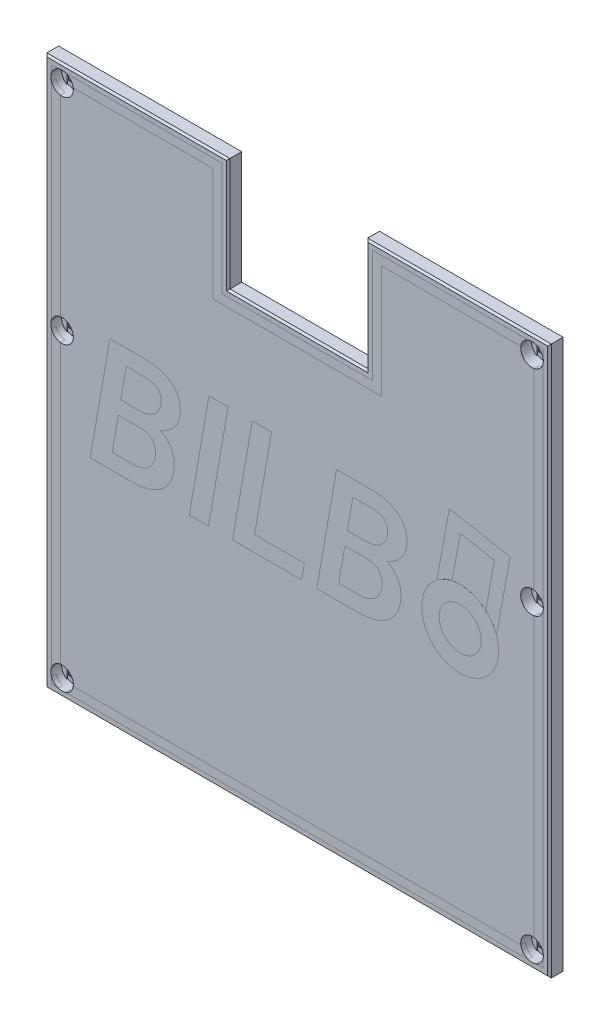
SolidWorks part; units mm, degrees
ref_plane "Front Plane" through (0, 0, 0) normal (0, 0, 1) x (1, 0, 0)
ref_plane "Top Plane" through (0, 0, 0) normal (0, 1, 0) x (1, 0, 0)
ref_plane "Right Plane" through (0, 0, 0) normal (1, 0, 0) x (0, 0, -1)
sketch "Sketch1" plane through (0, 0, 0) normal (0, 0, 1) x (1, 0, 0)
  line L0 (48, -68) -> (-48, -68) construction
  line L1 (56, -32.5) -> (56, -60) construction
  line L2 (56, 46) -> (56, -24.5) construction
  line L3 (-56, -24.5) -> (-56, 46) construction
  line L5 (-15, 54.4) -> (-15, 29) construction
  line L6 (-15, 29) -> (15, 29) construction
  line L8 (48, 54) -> (15, 54) construction
  line L9 (48, -68) -> (-48, -68) construction
  line L10 (56, -32.5) -> (56, -60) construction
  line L11 (56, 46) -> (56, -24.5) construction
  line L12 (-56, -24.5) -> (-56, 46) construction
  line L14 (-15, 54.4) -> (-15, 29) construction
  line L15 (-15, 29) -> (15, 29) construction
  line L16 (15, 29) -> (15, 54) construction
  line L17 (48, 54) -> (15, 54) construction
  line L18 (-15.25, 53.75) -> (-15.25, 28.75)
  line L19 (-55.75, 53.75) -> (-15.25, 53.75)
  line L20 (-55.75, 53.75) -> (-55.75, -67.75)
  line L21 (-55.75, -67.75) -> (55.875, -67.75)
  line L22 (55.875, 53.75) -> (55.875, -67.75)
  line L23 (-15.25, 28.75) -> (15.25, 28.75)
  line L24 (15.25, 28.75) -> (15.25, 53.75)
  line L25 (15.25, 53.75) -> (55.875, 53.75)
  circle A0 centre (-52, -64) radius 2.15 construction
  circle A3 centre (52, 50) radius 2.15 construction
  circle A4 centre (-52, 50) radius 2.15 construction
  circle A5 centre (-52, -64) radius 2.15 construction
  circle A6 centre (-52, 2.6) radius 2.15 construction
  circle A7 centre (52, 2.6) radius 2.15 construction
  circle A8 centre (52, 50) radius 2.15 construction
  circle A9 centre (-52, 50) radius 2.15 construction
  circle A10 centre (-52, 50) radius 1.35
  circle A11 centre (-52, 2.6) radius 1.35
  circle A12 centre (-52, -64) radius 1.35
  circle A13 centre (52, 50) radius 1.35
  circle A14 centre (52, 2.6) radius 1.35
  circle A15 centre (52, -64) radius 1.35
  circle A16 centre (-52, 2.6) radius 2.15 construction
  circle A17 centre (52, 2.6) radius 2.15 construction
  dimension "D5" = 2.7
  dimension "D1" = 0.25
  dimension "D2" = 0.25
  dimension "D3" = 0.25
  dimension "D4" = 0.25
  dimension "D6" = 0.25
  dimension "D7" = 0.25
  dimension "D8" = 0.25
extrude "Boss-Extrude1" add sketch "Sketch1" along normal blind 3
sketch "Sketch2" plane through (0, 0, 3) normal (0, 0, 1) x (1, 0, 0)
  line L5 (15.25, 28.75) -> (-15.25, 28.75) construction
  line L8 (-45.5, -63.25) -> (45.5, -63.25)
  line L9 (-45.5, -63.25) -> (-45.5, 27.75)
  line L10 (-45.5, 27.75) -> (45.5, 27.75)
  line L11 (45.5, -63.25) -> (45.5, 27.75)
  line L31 (-42, 24.25) -> (-28, 24.25)
  line L32 (-42, 24.25) -> (-42, 10.25)
  line L33 (-42, 10.25) -> (-28, 10.25)
  line L34 (-28, 24.25) -> (-28, 10.25)
  line L35 (-28, 24.25) -> (-14, 24.25)
  line L36 (-28, 24.25) -> (-28, 10.25)
  line L37 (-28, 10.25) -> (-14, 10.25)
  line L38 (-14, 24.25) -> (-14, 10.25)
  line L39 (-14, 24.25) -> (0, 24.25)
  line L40 (-14, 24.25) -> (-14, 10.25)
  line L41 (-14, 10.25) -> (0, 10.25)
  line L42 (0, 24.25) -> (0, 10.25)
  line L43 (0, 24.25) -> (14, 24.25)
  line L44 (0, 24.25) -> (0, 10.25)
  line L45 (0, 10.25) -> (14, 10.25)
  line L46 (14, 24.25) -> (14, 10.25)
  line L47 (14, 24.25) -> (28, 24.25)
  line L48 (14, 24.25) -> (14, 10.25)
  line L49 (14, 10.25) -> (28, 10.25)
  line L50 (28, 24.25) -> (28, 10.25)
  line L51 (28, 24.25) -> (42, 24.25)
  line L52 (28, 24.25) -> (28, 10.25)
  line L53 (28, 10.25) -> (42, 10.25)
  line L54 (42, 24.25) -> (42, 10.25)
  line L55 (-42, 10.25) -> (-28, 10.25)
  line L56 (-42, 10.25) -> (-42, -3.75)
  line L57 (-42, -3.75) -> (-28, -3.75)
  line L58 (-28, 10.25) -> (-28, -3.75)
  line L59 (-28, -3.75) -> (-14, -3.75)
  line L60 (-28, -3.75) -> (-28, 10.25)
  line L61 (-28, 10.25) -> (-14, 10.25)
  line L62 (-14, -3.75) -> (-14, 10.25)
  line L63 (-14, -3.75) -> (0, -3.75)
  line L64 (-14, -3.75) -> (-14, 10.25)
  line L65 (-14, 10.25) -> (0, 10.25)
  line L66 (0, -3.75) -> (0, 10.25)
  line L67 (0, -3.75) -> (14, -3.75)
  line L68 (0, -3.75) -> (0, 10.25)
  line L69 (0, 10.25) -> (14, 10.25)
  line L70 (14, -3.75) -> (14, 10.25)
  line L71 (14, -3.75) -> (28, -3.75)
  line L72 (14, -3.75) -> (14, 10.25)
  line L73 (14, 10.25) -> (28, 10.25)
  line L74 (28, -3.75) -> (28, 10.25)
  line L75 (28, -3.75) -> (42, -3.75)
  line L76 (28, -3.75) -> (28, 10.25)
  line L77 (28, 10.25) -> (42, 10.25)
  line L78 (42, -3.75) -> (42, 10.25)
  line L79 (42, -3.75) -> (28, -3.75)
  line L80 (42, -3.75) -> (42, -17.75)
  line L81 (42, -17.75) -> (28, -17.75)
  line L82 (28, -3.75) -> (28, -17.75)
  line L83 (14, -3.75) -> (28, -3.75)
  line L84 (14, -3.75) -> (14, -17.75)
  line L85 (14, -17.75) -> (28, -17.75)
  line L86 (28, -3.75) -> (28, -17.75)
  line L87 (0, -3.75) -> (14, -3.75)
  line L88 (0, -3.75) -> (0, -17.75)
  line L89 (0, -17.75) -> (14, -17.75)
  line L90 (14, -3.75) -> (14, -17.75)
  line L91 (-14, -3.75) -> (0, -3.75)
  line L92 (-14, -3.75) -> (-14, -17.75)
  line L93 (-14, -17.75) -> (0, -17.75)
  line L94 (0, -3.75) -> (0, -17.75)
  line L95 (-28, -3.75) -> (-14, -3.75)
  line L96 (-28, -3.75) -> (-28, -17.75)
  line L97 (-28, -17.75) -> (-14, -17.75)
  line L98 (-14, -3.75) -> (-14, -17.75)
  line L99 (-42, -3.75) -> (-28, -3.75)
  line L100 (-42, -3.75) -> (-42, -17.75)
  line L101 (-42, -17.75) -> (-28, -17.75)
  line L102 (-28, -3.75) -> (-28, -17.75)
  line L103 (-42, -17.75) -> (-28, -17.75)
  line L104 (-42, -17.75) -> (-42, -31.75)
  line L105 (-42, -31.75) -> (-28, -31.75)
  line L106 (-28, -17.75) -> (-28, -31.75)
  line L107 (-28, -31.75) -> (-14, -31.75)
  line L108 (-28, -31.75) -> (-28, -17.75)
  line L109 (-28, -17.75) -> (-14, -17.75)
  line L110 (-14, -31.75) -> (-14, -17.75)
  line L111 (-14, -17.75) -> (0, -17.75)
  line L112 (-14, -17.75) -> (-14, -31.75)
  line L113 (-14, -31.75) -> (0, -31.75)
  line L114 (0, -17.75) -> (0, -31.75)
  line L115 (0, -31.75) -> (14, -31.75)
  line L116 (0, -31.75) -> (0, -17.75)
  line L117 (0, -17.75) -> (14, -17.75)
  line L118 (14, -31.75) -> (14, -17.75)
  line L119 (14, -31.75) -> (28, -31.75)
  line L120 (14, -31.75) -> (14, -17.75)
  line L121 (14, -17.75) -> (28, -17.75)
  line L122 (28, -31.75) -> (28, -17.75)
  line L123 (28, -31.75) -> (42, -31.75)
  line L124 (28, -31.75) -> (28, -17.75)
  line L125 (28, -17.75) -> (42, -17.75)
  line L126 (42, -31.75) -> (42, -17.75)
  line L127 (-42, -31.75) -> (-28, -31.75)
  line L128 (-42, -31.75) -> (-42, -45.75)
  line L129 (-42, -45.75) -> (-28, -45.75)
  line L130 (-28, -31.75) -> (-28, -45.75)
  line L131 (-28, -45.75) -> (-14, -45.75)
  line L132 (-28, -45.75) -> (-28, -31.75)
  line L133 (-28, -31.75) -> (-14, -31.75)
  line L134 (-14, -45.75) -> (-14, -31.75)
  line L135 (-14, -45.75) -> (0, -45.75)
  line L136 (-14, -45.75) -> (-14, -31.75)
  line L137 (-14, -31.75) -> (0, -31.75)
  line L138 (0, -45.75) -> (0, -31.75)
  line L139 (0, -45.75) -> (14, -45.75)
  line L140 (0, -45.75) -> (0, -31.75)
  line L141 (0, -31.75) -> (14, -31.75)
  line L142 (14, -45.75) -> (14, -31.75)
  line L143 (14, -45.75) -> (28, -45.75)
  line L144 (14, -45.75) -> (14, -31.75)
  line L145 (14, -31.75) -> (28, -31.75)
  line L146 (28, -45.75) -> (28, -31.75)
  line L147 (28, -45.75) -> (42, -45.75)
  line L148 (28, -45.75) -> (28, -31.75)
  line L149 (28, -31.75) -> (42, -31.75)
  line L150 (42, -45.75) -> (42, -31.75)
  line L151 (42, -45.75) -> (28, -45.75)
  line L152 (42, -45.75) -> (42, -59.75)
  line L153 (42, -59.75) -> (28, -59.75)
  line L154 (28, -45.75) -> (28, -59.75)
  line L155 (28, -59.75) -> (14, -59.75)
  line L156 (28, -59.75) -> (28, -45.75)
  line L157 (28, -45.75) -> (14, -45.75)
  line L158 (14, -59.75) -> (14, -45.75)
  line L159 (0, -45.75) -> (14, -45.75)
  line L160 (0, -45.75) -> (0, -59.75)
  line L161 (0, -59.75) -> (14, -59.75)
  line L162 (14, -45.75) -> (14, -59.75)
  line L163 (-14, -45.75) -> (0, -45.75)
  line L164 (-14, -45.75) -> (-14, -59.75)
  line L165 (-14, -59.75) -> (0, -59.75)
  line L166 (0, -45.75) -> (0, -59.75)
  line L167 (-28, -45.75) -> (-14, -45.75)
  line L168 (-28, -45.75) -> (-28, -59.75)
  line L169 (-28, -59.75) -> (-14, -59.75)
  line L170 (-14, -45.75) -> (-14, -59.75)
  line L171 (-42, -45.75) -> (-28, -45.75)
  line L172 (-42, -45.75) -> (-42, -59.75)
  line L173 (-42, -59.75) -> (-28, -59.75)
  line L174 (-28, -45.75) -> (-28, -59.75)
  point P3 (0, 27.75)
  point P58 (-45.5, -17.75)
  dimension "D1" = 1
  dimension "D2" = 91
  dimension "D3" = 14
sketch "Sketch3" plane through (0, 0, 3) normal (0, 0, 1) x (1, 0, 0)
  circle A0 centre (-52, 50) radius 2.5
  circle A1 centre (-52, 2.6) radius 2.5
  circle A2 centre (-52, -64) radius 2.5
  circle A3 centre (52, -64) radius 2.5
  circle A4 centre (52, 2.6) radius 2.5
  circle A5 centre (52, 50) radius 2.5
  dimension "D1" = 5
extrude "Cut-Extrude1" cut sketch "Sketch3" against normal blind 2.4
sketch "Sketch4" plane through (0, 0, 0) normal (0, 0, -1) x (-1, 0, 0)
  line L0 (-15.25, 28.75) -> (15.25, 28.75) construction
  line L1 (-45.75, -57.75) -> (45.75, -57.75)
  line L2 (-45.75, -57.75) -> (-45.75, 27.75)
  line L3 (-45.75, 27.75) -> (45.75, 27.75)
  line L4 (45.75, -57.75) -> (45.75, 27.75)
  line L5 (-45.75, -57.75) -> (45.75, 27.75) construction
  line L6 (-45.75, 27.75) -> (45.75, -57.75) construction
  line L7 (55.75, 53.75) -> (55.75, -67.75) construction
  line L8 (55.75, -67.75) -> (-55.875, -67.75) construction
  point P0 (0, -15)
  point P9 (0, 27.75)
  dimension "D1" = 1
  dimension "D2" = 10
  dimension "D3" = 10
extrude "Cut-Extrude2" cut sketch "Sketch4" against normal blind 1.5
sketch "Sketch5" plane through (0, 0, 0.6) normal (0, 0, 1) x (1, 0, 0)
  line L2 (-53.35, 47.8958) -> (-53.35, 52.1042)
  line L4 (-50.65, 47.8958) -> (-50.65, 52.1042)
  line L5 (-53.35, 47.8958) -> (-50.65, 52.1042) construction
  line L6 (-53.35, 52.1042) -> (-50.65, 47.8958) construction
  line L8 (-53.35, 0.4958) -> (-53.35, 4.7042)
  line L10 (-50.65, 0.4958) -> (-50.65, 4.7042)
  line L11 (-53.35, 0.4958) -> (-50.65, 4.7042) construction
  line L12 (-53.35, 4.7042) -> (-50.65, 0.4958) construction
  line L14 (-53.35, -66.1042) -> (-53.35, -61.8958)
  line L16 (-50.65, -66.1042) -> (-50.65, -61.8958)
  line L17 (-53.35, -66.1042) -> (-50.65, -61.8958) construction
  line L18 (-53.35, -61.8958) -> (-50.65, -66.1042) construction
  circle A0 centre (-52, 50) radius 2.5 construction
  circle A1 centre (-52, 50) radius 1.35 construction
  arc A2 (-50.65, 52.1042) -> (-53.35, 52.1042) centre (-52, 50) ccw
  arc A3 (-53.35, 47.8958) -> (-50.65, 47.8958) centre (-52, 50) ccw
  circle A4 centre (-52, 2.6) radius 2.5 construction
  circle A5 centre (-52, 2.6) radius 1.35 construction
  circle A6 centre (-52, 2.6) radius 2.5 construction
  arc A7 (-50.65, 4.7042) -> (-53.35, 4.7042) centre (-52, 2.6) ccw
  arc A8 (-53.35, 0.4958) -> (-50.65, 0.4958) centre (-52, 2.6) ccw
  circle A9 centre (-52, -64) radius 2.5 construction
  circle A10 centre (-52, -64) radius 1.35 construction
  circle A11 centre (-52, -64) radius 2.5 construction
  arc A12 (-50.65, -61.8958) -> (-53.35, -61.8958) centre (-52, -64) ccw
  arc A13 (-53.35, -66.1042) -> (-50.65, -66.1042) centre (-52, -64) ccw
  point P0 (-52, 50)
  point P10 (-52, 2.6)
  point P22 (-52, -64)
extrude "Cut-Extrude3" cut sketch "Sketch5" against normal blind 0.2
sketch "Sketch6" plane through (0, 0, 0.4) normal (0, 0, 1) x (1, 0, 0)
  line L0 (-50.65, -66.1042) -> (-50.65, -61.8958) construction
  line L1 (-53.35, -65.35) -> (-50.65, -65.35)
  line L2 (-53.35, -65.35) -> (-53.35, -62.65)
  line L3 (-53.35, -62.65) -> (-50.65, -62.65)
  line L4 (-50.65, -65.35) -> (-50.65, -62.65)
  line L5 (-53.35, -65.35) -> (-50.65, -62.65) construction
  line L6 (-53.35, -62.65) -> (-50.65, -65.35) construction
  line L7 (-50.65, 0.4958) -> (-50.65, 4.7042) construction
  line L8 (-53.35, 1.25) -> (-50.65, 1.25)
  line L9 (-53.35, 1.25) -> (-53.35, 3.95)
  line L10 (-53.35, 3.95) -> (-50.65, 3.95)
  line L11 (-50.65, 1.25) -> (-50.65, 3.95)
  line L12 (-53.35, 1.25) -> (-50.65, 3.95) construction
  line L13 (-53.35, 3.95) -> (-50.65, 1.25) construction
  line L14 (-50.65, 47.8958) -> (-50.65, 52.1042) construction
  line L15 (-53.35, 48.65) -> (-50.65, 48.65)
  line L16 (-53.35, 48.65) -> (-53.35, 51.35)
  line L17 (-53.35, 51.35) -> (-50.65, 51.35)
  line L18 (-50.65, 48.65) -> (-50.65, 51.35)
  line L19 (-53.35, 48.65) -> (-50.65, 51.35) construction
  line L20 (-53.35, 51.35) -> (-50.65, 48.65) construction
  arc A0 (-50.65, -64) -> (-53.35, -64) centre (-52, -64) ccw construction
  arc A1 (-50.65, 2.6) -> (-53.35, 2.6) centre (-52, 2.6) ccw construction
  arc A2 (-50.65, 50) -> (-53.35, 50) centre (-52, 50) ccw construction
  point P0 (-52, -64)
  point P11 (-52, 2.6)
  point P22 (-52, 50)
extrude "Cut-Extrude4" cut sketch "Sketch6" against normal blind 0.2
mirror "Mirror1" about plane through (0, 0, 0) normal (1, 0, 0) of "Cut-Extrude4", "Cut-Extrude3"
chamfer "Chamfer1" distance 0.4 angle 45 8 edges at (0.0625, -67.75, 3) (55.875, -7, 3) (35.5625, 53.75, 3) (15.25, 41.25, 3) (0, 28.75, 3) (-15.25, 41.25, 3) (-35.5, 53.75, 3) (-55.75, -7, 3)
sketch "Sketch8" plane through (0, 0, 3) normal (0, 0, 1) x (1, 0, 0)
  line L16 (-54.35, 52.35) -> (-54.35, -66.35)
  line L17 (-54.35, -66.35) -> (54.475, -66.35)
  line L18 (54.475, -66.35) -> (54.475, 52.35)
  line L19 (54.475, 52.35) -> (16.65, 52.35)
  line L20 (16.65, 52.35) -> (16.65, 27.35)
  line L21 (16.65, 27.35) -> (-16.65, 27.35)
  line L22 (-16.65, 27.35) -> (-16.65, 52.35)
  line L23 (-16.65, 52.35) -> (-54.35, 52.35)
  line L24 (-54.35, 52.35) -> (-54.35, -66.35)
  line L25 (-54.35, -66.35) -> (54.475, -66.35)
  line L26 (54.475, -66.35) -> (54.475, 52.35)
  line L27 (54.475, 52.35) -> (16.65, 52.35)
  line L28 (16.65, 52.35) -> (16.65, 27.35)
  line L29 (16.65, 27.35) -> (-16.65, 27.35)
  line L30 (-16.65, 27.35) -> (-16.65, 52.35)
  line L31 (-16.65, 52.35) -> (-54.35, 52.35)
  line L40 (-52.35, 50.35) -> (-52.35, -64.35)
  line L41 (-52.35, -64.35) -> (52.475, -64.35)
  line L42 (52.475, -64.35) -> (52.475, 50.35)
  line L43 (52.475, 50.35) -> (18.65, 50.35)
  line L44 (18.65, 50.35) -> (18.65, 25.35)
  line L45 (18.65, 25.35) -> (-18.65, 25.35)
  line L46 (-18.65, 25.35) -> (-18.65, 50.35)
  line L47 (-18.65, 50.35) -> (-52.35, 50.35)
  line L48 (-52.35, 50.35) -> (-52.35, -64.35)
  line L49 (-52.35, -64.35) -> (52.475, -64.35)
  line L50 (52.475, -64.35) -> (52.475, 50.35)
  line L51 (52.475, 50.35) -> (18.65, 50.35)
  line L52 (18.65, 50.35) -> (18.65, 25.35)
  line L53 (18.65, 25.35) -> (-18.65, 25.35)
  line L54 (-18.65, 25.35) -> (-18.65, 50.35)
  line L55 (-18.65, 50.35) -> (-52.35, 50.35)
  dimension "D1" = 1
  dimension "D2" = 3
extrude "Cut-Extrude5" cut sketch "Sketch8" against normal blind 1
extrude "Boss-Extrude2" add sketch "Sketch8<2>" against normal up to surface (1 mm away) separate body up to face at (0, 43.0542, 2)
sketch "Sketch8<2>" plane through (0, 0, 3) normal (0, 0, 1) x (1, 0, 0) same geometry as "Sketch8"
sketch "Sketch9" plane through (0, 0, 3) normal (0, 0, 1) x (1, 0, 0)
  circle A0 centre (-52, 2.6) radius 2.5
  circle A1 centre (-52, 50) radius 2.5
  circle A2 centre (52, 50) radius 2.5
  circle A3 centre (52, 2.6) radius 2.5
  circle A4 centre (52, -64) radius 2.5
  circle A5 centre (-52, -64) radius 2.5
  arc A6 (-50.65, -61.8958) -> (-53.35, -61.8958) centre (-52, -64) ccw construction
extrude "Cut-Extrude6" cut sketch "Sketch9" against normal up to surface (2.4 mm away) up to face at (-50.075, 2.6, 0.6)
sketch "Sketch12" plane through (0, 0, 3) normal (0, 0, 1) x (1, 0, 0)
  line L0 (33.6922, 11.273) -> (47.1538, 8.834)
  line L1 (47.1538, 8.834) -> (44.1506, -7.7421)
  line L3 (30.974, -3.7298) -> (33.6922, 11.273)
  line L4 (-45.7664, -18.6769) -> (-41.4194, 6.3396)
  line L5 (-41.4194, 6.3396) -> (-33.7392, 6.3224)
  line L6 (-36.5914, -18.6769) -> (-45.7664, -18.6769)
  line L7 (-39.5638, -7.3885) -> (-40.9212, -15.2062)
  line L8 (-40.9212, -15.2062) -> (-36.4711, -15.2233)
  line L9 (-34.478, -7.4057) -> (-39.5638, -7.3885)
  line L10 (-39.014, -4.1927) -> (-35.1138, -4.2099)
  line L11 (-33.3784, 2.8174) -> (-37.7941, 2.8345)
  line L12 (-37.7941, 2.8345) -> (-39.014, -4.1927)
  line L13 (-19.5988, -18.6769) -> (-23.8254, -18.6769)
  line L14 (-23.8254, -18.6769) -> (-19.4785, 6.3396)
  line L15 (-19.4785, 6.3396) -> (-15.2518, 6.3396)
  line L16 (-15.2518, 6.3396) -> (-19.5988, -18.6769)
  line L17 (-9.4101, -15.2062) -> (1.6206, -15.2062)
  line L18 (1.6206, -15.2062) -> (1.002, -18.6769)
  line L19 (1.002, -18.6769) -> (-14.2553, -18.6769)
  line L20 (-14.2553, -18.6769) -> (-9.9083, 6.3396)
  line L21 (-9.9083, 6.3396) -> (-5.6645, 6.3396)
  line L22 (-5.6645, 6.3396) -> (-9.4101, -15.2062)
  line L23 (4.3868, -18.6769) -> (8.7337, 6.3396)
  line L24 (8.7337, 6.3396) -> (16.4139, 6.3224)
  line L25 (13.5618, -18.6769) -> (4.3868, -18.6769)
  line L26 (10.5894, -7.3885) -> (9.232, -15.2062)
  line L27 (9.232, -15.2062) -> (13.682, -15.2233)
  line L28 (15.6751, -7.4057) -> (10.5894, -7.3885)
  line L29 (11.1392, -4.1927) -> (15.0394, -4.2099)
  line L30 (16.7747, 2.8174) -> (12.3591, 2.8345)
  line L31 (12.3591, 2.8345) -> (11.1392, -4.1927)
  spline S0 degree 3 poles (-33.7392, 6.3224) (-31.036, 6.311) (-29.0086, 5.7211) (-27.6569, 4.5527) knots 0 0 0 0 1 1 1 1
  spline S1 degree 3 poles (-27.6569, 4.5527) (-26.2939, 3.3958) (-25.6925, 1.7865) (-25.8529, -0.2753) knots 0 0 0 0 1 1 1 1
  spline S2 degree 3 poles (-25.8529, -0.2753) (-26.0591, -2.7037) (-27.5424, -4.5306) (-30.3029, -5.7563) knots 0 0 0 0 1 1 1 1
  spline S3 degree 3 poles (-30.3029, -5.7563) (-29.272, -6.1228) (-28.4759, -6.7929) (-27.9147, -7.7665) knots 0 0 0 0 1 1 1 1
  spline S4 degree 3 poles (-27.9147, -7.7665) (-27.3534, -8.7402) (-27.1129, -9.9028) (-27.193, -11.2544) knots 0 0 0 0 1 1 1 1
  spline S5 degree 3 poles (-27.193, -11.2544) (-27.3534, -13.5453) (-28.2755, -15.3551) (-29.9593, -16.6838) knots 0 0 0 0 1 1 1 1
  spline S6 degree 3 poles (-29.9593, -16.6838) (-31.6316, -18.0125) (-33.8423, -18.6769) (-36.5914, -18.6769) knots 0 0 0 0 1 1 1 1
  spline S7 degree 3 poles (-36.4711, -15.2233) (-35.1309, -15.2233) (-33.9912, -14.8683) (-33.052, -14.1581) knots 0 0 0 0 1 1 1 1
  spline S8 degree 3 poles (-33.052, -14.1581) (-32.1127, -13.4479) (-31.5572, -12.4743) (-31.3854, -11.2372) knots 0 0 0 0 1 1 1 1
  spline S9 degree 3 poles (-31.3854, -11.2372) (-31.225, -10.0574) (-31.4025, -9.1353) (-31.918, -8.471) knots 0 0 0 0 1 1 1 1
  spline S10 degree 3 poles (-31.918, -8.471) (-32.4334, -7.8066) (-33.2868, -7.4515) (-34.478, -7.4057) knots 0 0 0 0 1 1 1 1
  spline S11 degree 3 poles (-35.1138, -4.2099) (-33.7163, -4.2099) (-32.5766, -3.8777) (-31.6946, -3.2134) knots 0 0 0 0 1 1 1 1
  spline S12 degree 3 poles (-31.6946, -3.2134) (-30.8126, -2.549) (-30.2915, -1.6499) (-30.1311, -0.5159) knots 0 0 0 0 1 1 1 1
  spline S13 degree 3 poles (-30.1311, -0.5159) (-29.8447, 1.6261) (-30.9272, 2.7372) (-33.3784, 2.8174) knots 0 0 0 0 1 1 1 1
  spline S14 degree 3 poles (16.4139, 6.3224) (19.1172, 6.311) (21.1446, 5.7211) (22.4962, 4.5527) knots 0 0 0 0 1 1 1 1
  spline S15 degree 3 poles (22.4962, 4.5527) (23.8593, 3.3958) (24.4606, 1.7865) (24.3003, -0.2753) knots 0 0 0 0 1 1 1 1
  spline S16 degree 3 poles (24.3003, -0.2753) (24.0941, -2.7037) (22.6108, -4.5306) (19.8502, -5.7563) knots 0 0 0 0 1 1 1 1
  spline S17 degree 3 poles (19.8502, -5.7563) (20.8812, -6.1228) (21.6772, -6.7929) (22.2385, -7.7665) knots 0 0 0 0 1 1 1 1
  spline S18 degree 3 poles (22.2385, -7.7665) (22.7998, -8.7402) (23.0403, -9.9028) (22.9601, -11.2544) knots 0 0 0 0 1 1 1 1
  spline S19 degree 3 poles (22.9601, -11.2544) (22.7998, -13.5453) (21.8777, -15.3551) (20.1939, -16.6838) knots 0 0 0 0 1 1 1 1
  spline S20 degree 3 poles (20.1939, -16.6838) (18.5215, -18.0125) (16.3108, -18.6769) (13.5618, -18.6769) knots 0 0 0 0 1 1 1 1
  spline S21 degree 3 poles (13.682, -15.2233) (15.0222, -15.2233) (16.1619, -14.8683) (17.1012, -14.1581) knots 0 0 0 0 1 1 1 1
  spline S22 degree 3 poles (17.1012, -14.1581) (18.0405, -13.4479) (18.596, -12.4743) (18.7678, -11.2372) knots 0 0 0 0 1 1 1 1
  spline S23 degree 3 poles (18.7678, -11.2372) (18.9282, -10.0574) (18.7506, -9.1353) (18.2352, -8.471) knots 0 0 0 0 1 1 1 1
  spline S24 degree 3 poles (18.2352, -8.471) (17.7197, -7.8066) (16.8664, -7.4515) (15.6751, -7.4057) knots 0 0 0 0 1 1 1 1
  spline S25 degree 3 poles (15.0394, -4.2099) (16.4368, -4.2099) (17.5765, -3.8777) (18.4585, -3.2134) knots 0 0 0 0 1 1 1 1
  spline S26 degree 3 poles (18.4585, -3.2134) (19.3405, -2.549) (19.8617, -1.6499) (20.0221, -0.5159) knots 0 0 0 0 1 1 1 1
  spline S27 degree 3 poles (20.0221, -0.5159) (20.3084, 1.6261) (19.226, 2.7372) (16.7747, 2.8174) knots 0 0 0 0 1 1 1 1
  spline S28 degree 3 poles (36.1069, -2.0072) (32.6655, -2.0072) (29.563, -4.0803) (28.2461, -7.2597) knots 0 0 0 0 1 1 1 1
  spline S29 degree 3 poles (28.2461, -7.2597) (26.9291, -10.4391) (27.6571, -14.0987) (30.0905, -16.5321) knots 0 0 0 0 1 1 1 1
  spline S30 degree 3 poles (30.0905, -16.5321) (32.5239, -18.9656) (36.1835, -19.6935) (39.363, -18.3766) knots 0 0 0 0 1 1 1 1
  spline S31 degree 3 poles (39.363, -18.3766) (42.5424, -17.0596) (44.6154, -13.9571) (44.6154, -10.5157) knots 0 0 0 0 1 1 1 1
  spline S32 degree 3 poles (44.6154, -10.5157) (44.6154, -8.2591) (43.719, -6.095) (42.1233, -4.4993) knots 0 0 0 0 1 1 1 1
  spline S33 degree 3 poles (42.1233, -4.4993) (40.5277, -2.9037) (38.3635, -2.0072) (36.1069, -2.0072) knots 0 0 0 0 1 1 1 1
  spline S34 degree 3 poles (36.1069, -5.8584) (34.2232, -5.8584) (32.525, -6.9931) (31.8041, -8.7335) knots 0 0 0 0 1 1 1 1
  spline S35 degree 3 poles (31.8041, -8.7335) (31.0832, -10.4738) (31.4817, -12.477) (32.8137, -13.809) knots 0 0 0 0 1 1 1 1
  spline S36 degree 3 poles (32.8137, -13.809) (34.1457, -15.1409) (36.1489, -15.5394) (37.8892, -14.8185) knots 0 0 0 0 1 1 1 1
  spline S37 degree 3 poles (37.8892, -14.8185) (39.6295, -14.0977) (40.7642, -12.3994) (40.7642, -10.5157) knots 0 0 0 0 1 1 1 1
  spline S38 degree 3 poles (40.7642, -10.5157) (40.7642, -9.2805) (40.2735, -8.0959) (39.4001, -7.2225) knots 0 0 0 0 1 1 1 1
  spline S39 degree 3 poles (39.4001, -7.2225) (38.5267, -6.3491) (37.3421, -5.8584) (36.1069, -5.8584) knots 0 0 0 0 1 1 1 1
extrude "Cut-Extrude8" cut sketch "Sketch12" against normal blind 1 contours S32 S33 S28 S29 S30 S31 S39 S38 S37 S36 S35 S34 | S20 S19 S18 S17 S16 S15 S14 L24 L23 L25 S27 S26 S25 L29 L31 L30 S24 S23 S22 S21 L27 L26 L28 | L22 L21 L20 L19 L18 L17 | L16 L15 L14 L13 | S6 S5 S4 S3 S2 S1 S0 L5 L4 L6 S13 S12 S11 L10 L12 L11 S10 S9 S8 S7 L8 L7 L9 region at (33.4763, -2.6772, 3) region at (-35.8032, -6.3189, 3) region at (-19.5386, -6.1686, 3) region at (-8.4341, -9.022, 3) region at (14.35, -6.3189, 3)
extrude "Boss-Extrude4" add sketch "Sketch12<3>" against normal up to surface (1 mm away) separate body contours S6 S5 S4 S3 S2 S1 S0 L5 L4 L6 S13 S12 S11 L10 L12 L11 S10 S9 S8 S7 L8 L7 L9 | L16 L15 L14 L13 | L22 L21 L20 L19 L18 L17 | S20 S19 S18 S17 S16 S15 S14 L24 L23 L25 S27 S26 S25 L29 L31 L30 S24 S23 S22 S21 L27 L26 L28 | S32 S33 S28 S29 S30 S31 S39 S38 S37 S36 S35 S34 region at (33.4763, -2.6772, 3) region at (-35.8032, -6.3189, 3) region at (-19.5386, -6.1686, 3) region at (-8.4341, -9.022, 3) region at (14.35, -6.3189, 3) up to face at (-34.6656, -1.6656, 2)
sketch "Sketch12<3>" plane through (0, 0, 3) normal (0, 0, 1) x (1, 0, 0) same geometry as "Sketch12"
sketch "Sketch13" plane through (0, 0, 3) normal (0, 0, 1) x (1, 0, 0)
  line L0 (47.1538, 8.834) -> (44.1506, -7.7421) construction
  line L1 (33.6922, 11.273) -> (47.1538, 8.834) construction
  line L2 (30.974, -3.7298) -> (33.6922, 11.273) construction
  line L3 (47.1538, 8.834) -> (44.1506, -7.7421)
  line L4 (33.6922, 11.273) -> (47.1538, 8.834)
  line L5 (30.974, -3.7298) -> (33.6922, 11.273)
  line L6 (34.2999, -2.2009) -> (36.1093, 7.7862)
  line L7 (36.1093, 7.7862) -> (43.6671, 6.4169)
  line L8 (43.6671, 6.4169) -> (41.7525, -4.1501)
  spline S0 degree 3 poles (-1189.0654, -1573.4794) (1598.8693, 1295.449) (-1768.4966, -954.5651) (1948.9836, 523.2965) knots -9.958619 -9.958619 -9.958619 -9.958619 10.95869 10.95869 10.95869 10.95869 only from (36.1069, -2.0072) to (28.2461, -7.2597) construction
  spline S1 degree 3 poles (-1945.6531, 129.6639) (1990.0799, -580.709) (-1748.7386, 967.9834) (1536.5332, -1312.7265) knots -15.185492 -15.185492 -15.185492 -15.185492 16.18548 16.18548 16.18548 16.18548 only from (42.1233, -4.4993) to (36.1069, -2.0072) construction
  spline S2 degree 3 poles (-1266.1037, 1489.9102) (1014.609, -1795.3654) (-534.0906, 1943.4673) (176.2894, -1992.2919) knots -15.185479 -15.185479 -15.185479 -15.185479 16.185535 16.185535 16.185535 16.185535 only from (44.6154, -10.5157) to (42.1233, -4.4993) construction
  spline S3 degree 3 poles (34.2999, -2.2009) (33.0841, -2.465) (31.9508, -2.9912) (30.974, -3.7298) knots 0.17899 0.17899 0.17899 0.17899 0.550361 0.550361 0.550361 0.550361
  spline S4 degree 3 poles (42.1233, -4.4993) (42.0029, -4.3789) (41.8792, -4.2625) (41.7525, -4.1501) knots 0 0 0 0 0.075465 0.075465 0.075465 0.075465
  spline S5 degree 3 poles (44.1506, -7.7421) (43.7335, -6.5326) (43.0451, -5.4211) (42.1233, -4.4993) knots 0.422315 0.422315 0.422315 0.422315 1 1 1 1
  point P10 (44.6154, 6.245)
  point P13 (0, 0)
  dimension "D1" = 3
  dimension "D2" = 3
  dimension "D3" = 3
extrude "Cut-Extrude9" cut sketch "Sketch13" against normal blind 1
extrude "Boss-Extrude5" add sketch "Sketch13<2>" against normal up to surface (1 mm away) separate body up to face at (36.4622, -5.2554, 2)
sketch "Sketch13<2>" plane through (0, 0, 3) normal (0, 0, 1) x (1, 0, 0) same geometry as "Sketch13"
